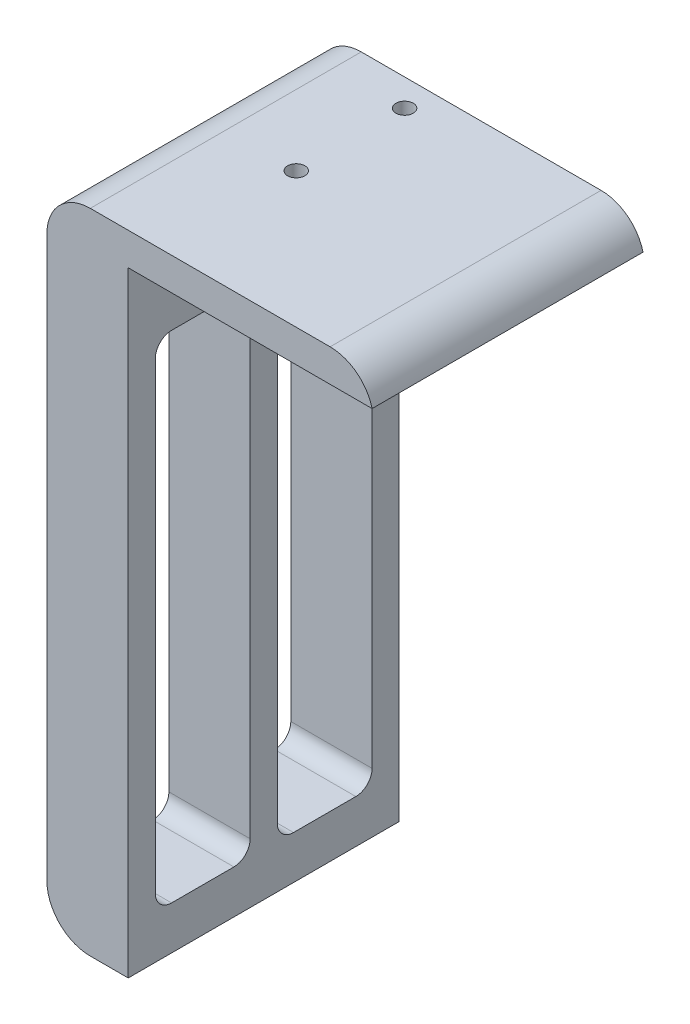
SolidWorks part; units mm, degrees
ref_plane "前视基准面" through (0, 0, 0) normal (0, 0, 1) x (1, 0, 0)
ref_plane "上视基准面" through (0, 0, 0) normal (0, 1, 0) x (1, 0, 0)
ref_plane "右视基准面" through (0, 0, 0) normal (1, 0, 0) x (0, 0, -1)
other "Configuration Table"
sketch "草图1" plane through (0, 0, 0) normal (0, 0, 1) x (1, 0, 0)
  line L0 (0, 0) -> (0, 119.5)
  line L1 (0, 119.5) -> (15, 119.5)
  line L2 (15, 119.5) -> (15, 6)
  line L3 (15, 6) -> (60, 6)
  line L4 (60, 6) -> (60, 0)
  line L5 (60, 0) -> (0, 0)
  dimension "D1" = 6
  dimension "D2" = 15
  dimension "D3" = 60
  dimension "D4" = 119.5
extrude "凸台-拉伸1" add sketch "草图1" along normal mid plane 50
fillet "圆角1" radius 8 3 edges at (0, 119.5, 0) (60, 0, 0) (0, 0, 0)
sketch "草图2" plane through (0, 0, 0) normal (-1, 0, 0) x (0, 0, 1)
  line L0 (0, 0) -> (0, 33.7003) construction
  line L2 (25, 0) -> (-25, 0) construction
  circle A0 centre (10, 12) radius 1.65
  circle A1 centre (-10, 12) radius 1.65
  dimension "D1" = 3.3
  dimension "D2" = 12
  dimension "D3" = 20
extrude "切除-拉伸1" cut sketch "草图2" against normal through all
sketch "草图3" plane through (0, 6, 0) normal (0, 1, 0) x (1, 0, 0)
  line L0 (21, 20) -> (21, 0) construction
  line L1 (60, 25) -> (15, 25) construction
  circle A0 centre (21, 0) radius 1.6
  circle A1 centre (21, 20) radius 1.6
  dimension "D1" = 3.2
  dimension "D2" = 20
  dimension "D3" = 5
  dimension "D4" = 21
extrude "切除-拉伸2" cut sketch "草图3" against normal through all
sketch "草图4" plane through (0, 0, 0) normal (-1, 0, 0) x (0, 0, 1)
  line L0 (-20, 111.5) -> (-20, 20)
  line L1 (-20, 20) -> (-2.5, 20)
  line L2 (-2.5, 20) -> (-2.5, 111.5)
  line L3 (-2.5, 111.5) -> (-20, 111.5)
  line L4 (0, 0) -> (0, 123.1134) construction
  line L5 (25, 0) -> (-25, 0) construction
  line L6 (-25, 111.5) -> (-25, 8) construction
  line L7 (-25, 119.5) -> (25, 119.5) construction
  line L8 (2.5, 111.5) -> (20, 111.5)
  line L9 (2.5, 20) -> (2.5, 111.5)
  line L10 (20, 20) -> (2.5, 20)
  line L11 (20, 111.5) -> (20, 20)
  dimension "D1" = 5
  dimension "D2" = 5
  dimension "D3" = 8
  dimension "D4" = 20
extrude "切除-拉伸3" cut sketch "草图4" against normal through all
fillet "圆角2" radius 3 8 edges at (7.5, 111.5, -2.5) (7.5, 111.5, -20) (7.5, 111.5, 20) (7.5, 111.5, 2.5) (7.5, 20, 20) (7.5, 20, 2.5) (7.5, 20, -20) (7.5, 20, -2.5)
mirror "镜向1" about plane through (0, 119.5, 25) normal (0, -1, 0) of bodies 112
delete or keep bodies "实体-删除/保留 1" type delete bodies bodies 112
